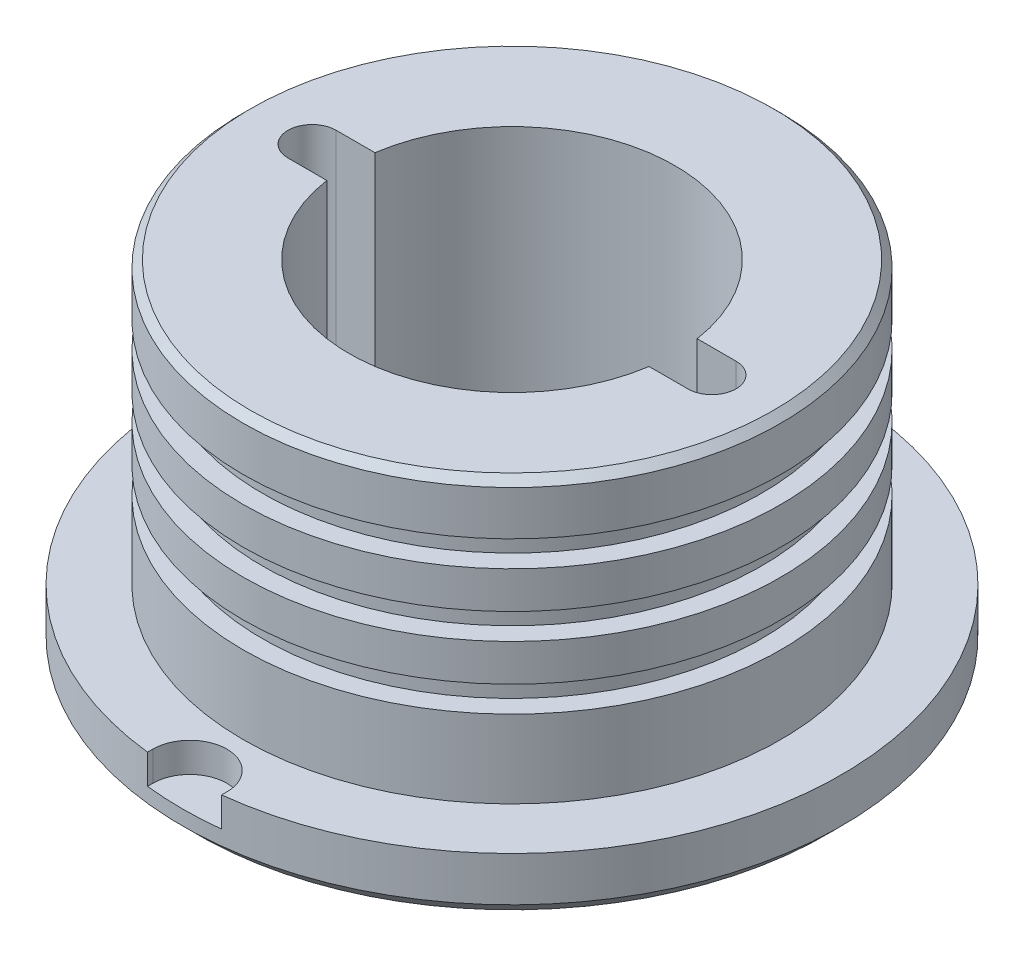
SolidWorks part; units mm, degrees
ref_plane "Plano frontal" through (0, 0, 0) normal (0, 0, 1) x (1, 0, 0)
ref_plane "Plano superior" through (0, 0, 0) normal (0, 1, 0) x (1, 0, 0)
ref_plane "Plano direito" through (0, 0, 0) normal (1, 0, 0) x (0, 0, -1)
sketch "Esboço1" plane through (0, 0, 0) normal (0, 0, 1) x (1, 0, 0)
  line L19 (0, 0) -> (0, 111187.7924) construction
  line L34 (44.5, 0) -> (44.5, 8)
  line L35 (44.5, 8) -> (36.3, 8)
  line L41 (36.3, 18.5) -> (33.7, 18.5)
  line L42 (33.7, 18.5) -> (33.7, 22)
  line L43 (33.7, 22) -> (36.3, 22)
  line L44 (36.3, 22) -> (36.3, 27)
  line L45 (36.3, 27) -> (33.7, 27)
  line L46 (33.7, 27) -> (33.7, 30.5)
  line L47 (33.7, 30.5) -> (36.3, 30.5)
  line L48 (36.3, 30.5) -> (36.3, 35.5)
  line L49 (36.3, 35.5) -> (33.7, 35.5)
  line L50 (33.7, 35.5) -> (33.7, 39)
  line L51 (33.7, 39) -> (36.3, 39)
  line L52 (36.3, 39) -> (36.3, 46)
  line L53 (36.3, 46) -> (22, 46)
  line L55 (22, 46) -> (22, 12)
  line L83 (22, 12) -> (0, 12)
  line L84 (0, 12) -> (0, 0)
  line L85 (0, 0) -> (44.5, 0)
  line L86 (36.3, 18.5) -> (36.3, 8)
  point P49 (0, 0)
  dimension "D1" = 8
  dimension "D2" = 10.5
  dimension "D4" = 3.5
  dimension "D5" = 7
  dimension "D6" = 89
  dimension "D7" = 72.6
  dimension "D8" = 67.4
  dimension "D9" = 5
  dimension "D10" = 12
  dimension "D11" = 44
revolve "Revolução1" add sketch "Esboço1" angle 360 about L19
sketch "Esboço2" plane through (0, 8, 0) normal (0, 1, 0) x (1, 0, 0)
  line L0 (0, 44.5) -> (0, -44.5) construction
  line L4 (0, 0) -> (44.5, 0) construction
  line L8 (0, 45.5) -> (0, 43.5) construction
  line L11 (5, 45.5) -> (5, 43.5)
  line L12 (-5, 45.5) -> (-5, 43.5)
  line L13 (0, -45.5) -> (0, -43.5) construction
  line L14 (5, -45.5) -> (5, -43.5)
  line L15 (-5, -45.5) -> (-5, -43.5)
  circle A3 centre (0, 0) radius 44.5 construction
  arc A5 (5, 45.5) -> (-5, 45.5) centre (0, 45.5) ccw
  arc A6 (-5, 43.5) -> (5, 43.5) centre (0, 43.5) ccw
  arc A7 (5, -45.5) -> (-5, -45.5) centre (0, -45.5) cw
  arc A8 (-5, -43.5) -> (5, -43.5) centre (0, -43.5) cw
  point P3 (0, 44.5)
  point P13 (0, -44.5)
  dimension "D1" = 5
  dimension "D2" = 6
extrude "Corte-extrusão1" cut sketch "Esboço2" against normal blind 4
chamfer "Chanfro1" distance 1 angle 45 1 edges at (0, 46, -36.3)
sketch "Esboço3" plane through (0, 0, 0) normal (0, -1, 0) x (1, 0, 0)
  line L0 (0, 0) -> (0, 5.1187) construction
  line L1 (-27, 0) -> (-21.5, 0) construction
  line L2 (27, 0) -> (21.5, 0) construction
  line L3 (-27, 3.25) -> (-21.5, 3.25)
  line L4 (-27, -3.25) -> (-21.5, -3.25)
  line L5 (27, 3.25) -> (21.5, 3.25)
  line L6 (27, -3.25) -> (21.5, -3.25)
  circle A0 centre (0, 0) radius 27 construction
  circle A1 centre (-27, 0) radius 1.5
  circle A3 centre (27, 0) radius 1.5
  arc A9 (-27, 3.25) -> (-27, -3.25) centre (-27, 0) ccw
  arc A10 (-21.5, -3.25) -> (-21.5, 3.25) centre (-21.5, 0) ccw
  arc A11 (27, 3.25) -> (27, -3.25) centre (27, 0) cw
  arc A12 (21.5, -3.25) -> (21.5, 3.25) centre (21.5, 0) cw
  point P9 (24.25, 0)
  point P15 (-24.25, 0)
  dimension "D1" = 54
  dimension "D2" = 3
  dimension "D3" = 6.5
  dimension "D4" = 12
extrude "Corte-extrusão2" cut sketch "Esboço3" against normal up to surface (12 mm away) and the other way through all contours A1 | A3 up to face at (0, 12, -22)
extrude "Corte-extrusão3" cut sketch "Esboço3<5>" against normal through all from surface contours A1 | A1 | A3 | A3 region at (-23.9358, 0, 0) region at (23.9358, 0, 0) region at (-27, 0, 0) region at (27, 0, 0) starting at face at (0, 12, -22)
sketch "Esboço3<5>" plane through (0, 0, 0) normal (0, -1, 0) x (1, 0, 0) same geometry as "Esboço3"
chamfer "Chanfro2" distance 2 angle 45 1 edges at (0, 0, -44.5)
sketch "Esboço4" plane through (0, 0, 0) normal (0, -1, 0) x (1, 0, 0)
  line L0 (0, 42.5) -> (0, -42.5) construction
  line L1 (-8.5, 7) -> (8.5, 7) construction
  line L2 (0, 0) -> (42.5, 0) construction
  circle A0 centre (0, 0) radius 42.5 construction
  circle A1 centre (-8.5, 7) radius 1.25
  circle A2 centre (8.5, 7) radius 1.25
  circle A5 centre (0, -13) radius 4
  point P9 (0, 7)
  dimension "D1" = 2.5
  dimension "D2" = 2.5
  dimension "D5" = 8
  dimension "D6" = 13
  dimension "D3" = 17
  dimension "D4" = 7
extrude "Corte-extrusão4" cut sketch "Esboço4" against normal blind 6 contours A1 | A2 region at (-8.5, 0, 7) region at (8.5, 0, 7)
cosmetic thread "Representação de rosca2" parameters "D2"=3
cosmetic thread "Representação de rosca3" parameters "D2"=3
extrude "Corte-extrusão5" cut sketch "Esboço4<3>" against normal up to next contours A5
sketch "Esboço4<3>" plane through (0, 0, 0) normal (0, -1, 0) x (1, 0, 0) same geometry as "Esboço4"
cosmetic thread "Representação de rosca1" parameters "D2"=12.7
